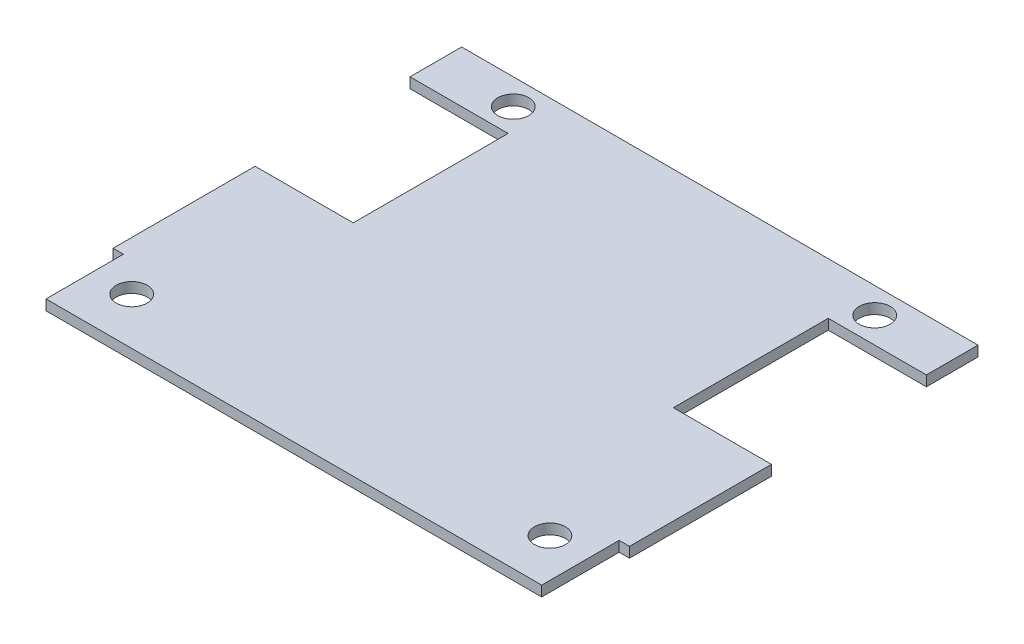
SolidWorks part; units mm, degrees
ref_plane "Alzado" through (0, 0, 0) normal (0, 0, 1) x (1, 0, 0)
ref_plane "Planta" through (0, 0, 0) normal (0, 1, 0) x (1, 0, 0)
ref_plane "Vista lateral" through (0, 0, 0) normal (1, 0, 0) x (0, 0, -1)
sketch "Croquis3" plane through (0, 0, 0) normal (0, 1, 0) x (1, 0, 0)
  line L0 (-190.4327, 32.5) -> (202.9714, 32.5) construction
  line L1 (-100, 82.5) -> (100, 82.5)
  line L2 (-100, 82.5) -> (-100, -82.5)
  line L3 (-100, -82.5) -> (100, -82.5)
  line L4 (100, 82.5) -> (100, -82.5)
  line L5 (-100, 82.5) -> (100, -82.5) construction
  line L6 (-100, -82.5) -> (100, 82.5) construction
  line L7 (0, 144.1781) -> (0, -169.0183) construction
  line L8 (100, 62.5) -> (62, 62.5)
  line L13 (-100, 2.5) -> (-62, 2.5)
  line L14 (-100, 2.5) -> (-100, 62.5)
  line L15 (-100, 62.5) -> (-62, 62.5)
  line L16 (-62, 2.5) -> (-62, 62.5)
  line L17 (62, 2.5) -> (62, 62.5)
  line L18 (100, 2.5) -> (62, 2.5)
  line L19 (100, 2.5) -> (100, 62.5)
  circle A0 centre (-70, 72.5) radius 6
  circle A1 centre (70, 72.5) radius 6
  point P0 (0, 0)
  dimension "D8" = 12
  dimension "D9" = 10
  dimension "D1" = 165
  dimension "D2" = 200
  dimension "D3" = 50
  dimension "D4" = 100
  dimension "D5" = 38
  dimension "D6" = 60
  dimension "D7" = 30
  dimension "D10" = 30
extrude "Saliente-Extruir1" add sketch "Croquis3" along normal blind 4 contours L4 L18 L17 L8 L1 L2 L15 L16 L13 L3 region at (0, 0, 5.834)
sketch "Croquis4" plane through (0, 4, 0) normal (0, 1, 0) x (1, 0, 0)
  line L0 (100, 2.5) -> (100, -82.5) construction
  line L1 (100, -52.5) -> (96, -52.5)
  line L2 (100, -52.5) -> (100, -82.5)
  line L3 (100, -82.5) -> (96, -82.5)
  line L4 (96, -52.5) -> (96, -82.5)
  line L5 (-100, -82.5) -> (100, -82.5) construction
  line L6 (0, 0) -> (0, -82.5) construction
  line L7 (-100, 82.5) -> (100, 82.5) construction
  line L8 (-100, -82.5) -> (-96, -82.5)
  line L9 (-100, -52.5) -> (-100, -82.5)
  line L10 (-100, -52.5) -> (-96, -52.5)
  line L11 (-96, -52.5) -> (-96, -82.5)
  dimension "D1" = 135
  dimension "D2" = 4
extrude "Cortar-Extruir1" cut sketch "Croquis4" against normal up to next
sketch "Croquis6" plane through (0, 4, 0) normal (0, 1, 0) x (1, 0, 0)
  line L0 (-96, -82.5) -> (-96, -52.5) construction
  line L1 (-100, -74.3092) -> (100, -74.3092) construction
  line L2 (96, -52.5) -> (96, -82.5) construction
  circle A0 centre (-81, -64.3092) radius 6
  circle A1 centre (81, -64.3092) radius 6
  dimension "D1" = 12
  dimension "D2" = 15
  dimension "D3" = 10
  dimension "D5" = 15
extrude "Cortar-Extruir2" cut sketch "Croquis6" against normal blind 10
